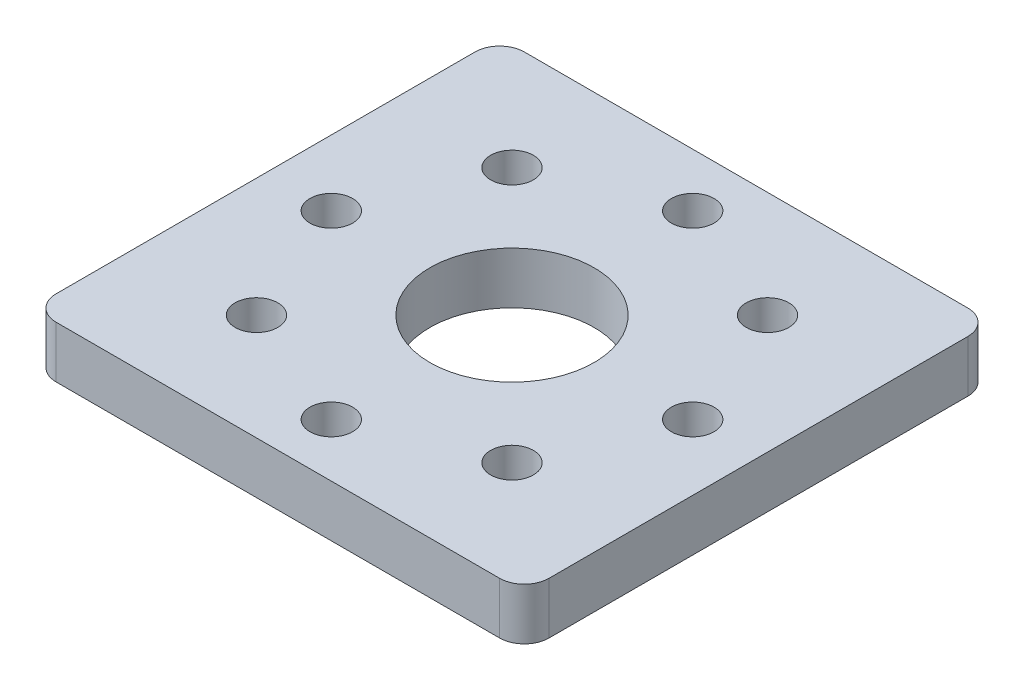
SolidWorks part; units mm, degrees
ref_plane "Front Plane" through (0, 0, 0) normal (0, 0, 1) x (1, 0, 0)
ref_plane "Top Plane" through (0, 0, 0) normal (0, 1, 0) x (1, 0, 0)
ref_plane "Right Plane" through (0, 0, 0) normal (1, 0, 0) x (0, 0, -1)
sketch "Sketch1" plane through (0, 0, 0) normal (0, 1, 0) x (1, 0, 0)
  line L1 (-15, 14.25) -> (15, 14.25)
  line L2 (-15, 14.25) -> (-15, -14.25)
  line L3 (-15, -14.25) -> (15, -14.25)
  line L4 (15, 14.25) -> (15, -14.25)
  dimension "D1" = 30
  dimension "D2" = 28.5
  dimension "D3" = 15
  dimension "D4" = 14.25
extrude "Boss-Extrude1" add sketch "Sketch1" against normal blind 3.15
sketch "Sketch2" plane through (0, 0, 0) normal (0, 1, 0) x (1, 0, 0)
  circle A0 centre (0, 0) radius 5
  circle A1 centre (0, 11) radius 1.3
  circle A2 centre (7.7782, 7.7782) radius 1.3
  circle A3 centre (11, 0) radius 1.3
  circle A4 centre (7.7782, -7.7782) radius 1.3
  circle A5 centre (0, -11) radius 1.3
  circle A6 centre (-7.7782, -7.7782) radius 1.3
  circle A7 centre (-11, 0) radius 1.3
  circle A8 centre (-7.7782, 7.7782) radius 1.3
  point P22 (0, 0)
  dimension "D1" = 10
  dimension "D2" = 2.6
  dimension "D3" = 11
  dimension "D4" = 8
extrude "Cut-Extrude1" cut sketch "Sketch2" against normal through all
fillet "Fillet1" radius 1.5 4 edges at (15, -1.575, 14.25) (-15, -1.575, 14.25) (-15, -1.575, -14.25) (15, -1.575, -14.25)
equation "\"PLATE_WIDTH1\"= 30"
equation "\"D1@Sketch1\"=\"PLATE_WIDTH1\""
equation "\"PLATE_WIDTH2\"=28.5"
equation "\"D3@Sketch1\"=\"D1@Sketch1\"/2"
equation "\"D4@Sketch1\"=\"D2@Sketch1\"/2"
